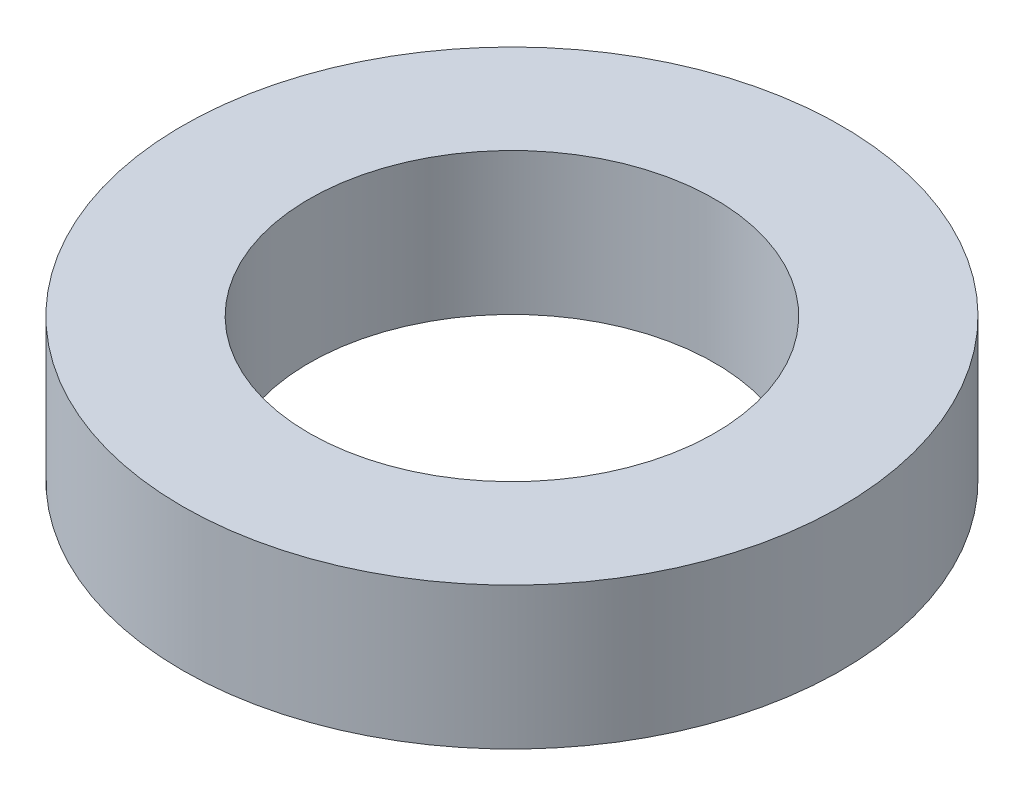
SolidWorks part; units mm, degrees
ref_plane "Front Plane" through (0, 0, 0) normal (0, 0, 1) x (1, 0, 0)
ref_plane "Top Plane" through (0, 0, 0) normal (0, 1, 0) x (1, 0, 0)
ref_plane "Right Plane" through (0, 0, 0) normal (1, 0, 0) x (0, 0, -1)
sketch "Sketch1" plane through (0, 0, 0) normal (0, 1, 0) x (1, 0, 0)
  circle A0 centre (0, 0) radius 65
  dimension "FLANGE_OD" = 130
extrude "Boss-Extrude1" add sketch "Sketch1" along normal blind 28
sketch "Sketch2" plane through (0, 0, 0) normal (0, 1, 0) x (1, 0, 0)
  circle A0 centre (0, 0) radius 40
  dimension "BORE_D" = 80
extrude "Cut-Extrude1" cut sketch "Sketch2" along normal through all
sketch "Sketch3" plane through (0, 28, 0) normal (0, 1, 0) x (1, 0, 0)
  circle A0 centre (0, 0) radius 25.8283 construction
  circle A1 centre (-25.8283, 0) radius 3.6248
  dimension "BOLT_D" = 7.2497
  dimension "BOLT_PCD" = 51.6566
extrude "Cut-Extrude2" cut sketch "Sketch3" against normal blind 18.7247 rebuild error yes
pattern_circular "CirPattern1" count 6 over 360 rebuild error yes
